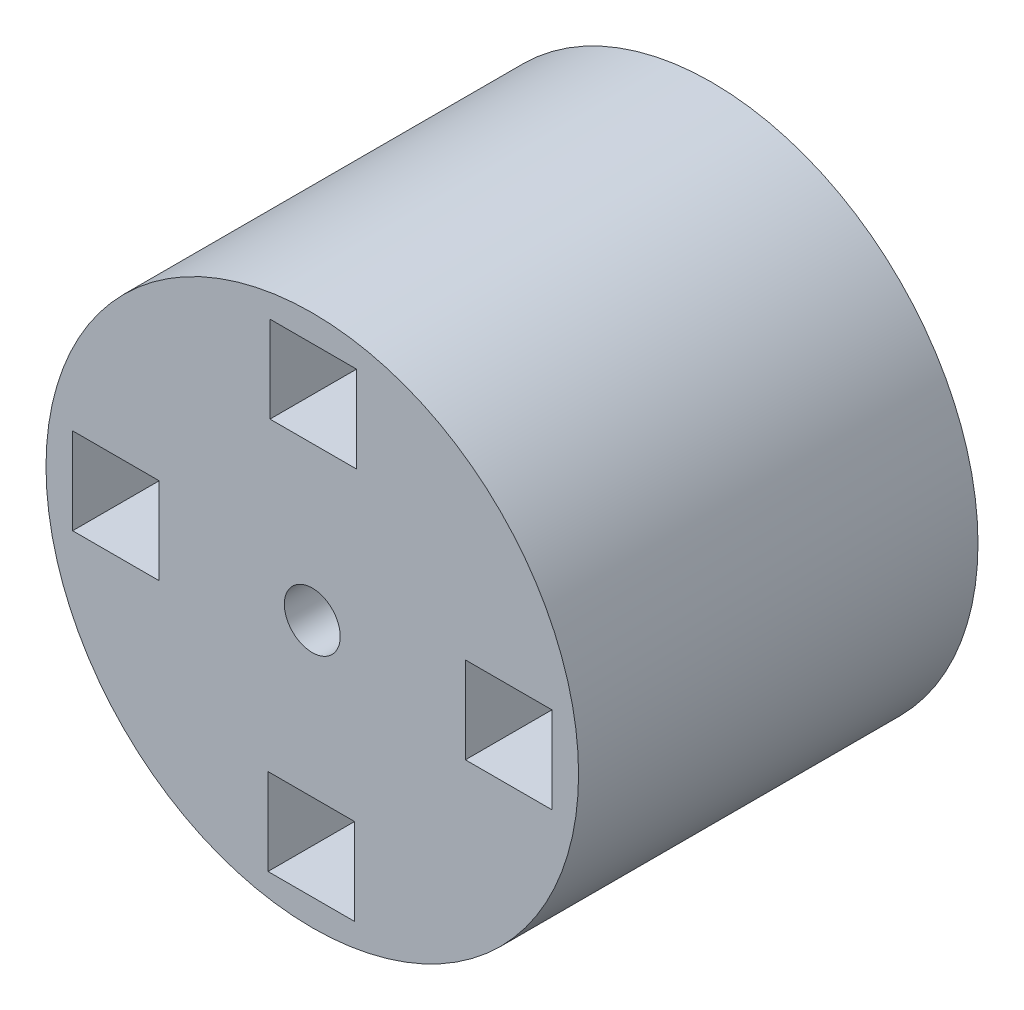
SolidWorks part; units mm, degrees
ref_plane "Front Plane" through (0, 0, 0) normal (0, 0, 1) x (1, 0, 0)
ref_plane "Top Plane" through (0, 0, 0) normal (0, 1, 0) x (1, 0, 0)
ref_plane "Right Plane" through (0, 0, 0) normal (1, 0, 0) x (0, 0, -1)
sketch "Sketch1" plane through (0, 0, 0) normal (0, 0, 1) x (1, 0, 0)
  circle A0 centre (-11.8226, 14.5298) radius 20
  circle A1 centre (-11.8226, 14.5298) radius 1
  dimension "D1" = 40
  dimension "D2" = 2
extrude "Boss-Extrude1" add sketch "Sketch1" along normal blind 30
hole_wizard "Tap Drill for M5x0.8 Tap1" positions "Sketch2" profile "Sketch3" hole size "M5x0.8" standard "ANSI Metric"
sketch "Sketch2" plane through (0, 0, 30) normal (0, 0, 1) x (1, 0, 0)
  point P0 (-11.8226, 14.5298)
sketch "Sketch3" plane through (-11.8226, 14.5298, 30) normal (1, 0, 0) x (0, -1, 0)
  line L0 (0, 0) -> (0, 6.2618)
  line L1 (0, 6.2618) -> (2.1, 5)
  line L2 (2.1, 5) -> (2.1, 0)
  line L5 (2.1, 0) -> (0, 0)
  line L10 (0, 6.2618) -> (-2.1, 5) construction
  line L11 (0, -6.35) -> (0, 107.95) construction
  dimension "Hole Dia." = 4.2
  dimension "Hole Depth" = 5
  dimension "Drill Angle" = 118
sketch "Sketch4" plane through (0, 0, 30) normal (0, 0, 1) x (1, 0, 0)
  line L1 (6.1774, 17.7048) -> (-0.3226, 17.7048)
  line L2 (6.1774, 17.7048) -> (6.1774, 11.2048)
  line L3 (6.1774, 11.2048) -> (-0.3226, 11.2048)
  line L4 (-0.3226, 17.7048) -> (-0.3226, 11.2048)
  circle A0 centre (-11.8226, 14.5298) radius 1 construction
  circle A1 centre (-11.8226, 14.5298) radius 20 construction
  dimension "D1" = 6.5
  dimension "D2" = 6.5
  dimension "D3" = 3.325
  dimension "D4" = 18
extrude "Cut-Extrude1" cut sketch "Sketch4" against normal offset from surface (27.5 mm away) 2.5 up to face at (8.1774, 14.5298, 0)
ref_axis "Axis1" through (-11.8226, 14.5298, 30) along (0, 0, -1)
pattern_circular "CirPattern1" count 4 over 360 about axis through (-11.8226, 14.5298, 30) along (0, 0, -1) of "Cut-Extrude1"
sketch "Sketch5" plane through (0, 0, 0) normal (0, 0, -1) x (-1, 0, 0)
  circle A0 centre (11.8226, 14.5298) radius 5.5
  circle A1 centre (11.8226, 14.5298) radius 6.5
  dimension "D1" = 11
  dimension "D2" = 13
extrude "Cut-Extrude2" cut sketch "Sketch5" against normal blind 1
fillet "Fillet3" radius 0.5 2 edges at (-17.3226, 14.5298, 1) (-18.3226, 14.5298, 1)
equation "\"D2@Sketch4\"=6.5"
equation "\"D3@Sketch4\"=6.65/2"
equation "\"oringdiameter\"= 12"
equation "\"oringthickness\"= 2"
equation "\"D2@Sketch5\"=\"oringdiameter\" + \"oringthickness\"/2"
equation "\"D1@Sketch5\"=\"oringdiameter\" - \"oringthickness\"/2"
equation "\"D1@Cut-Extrude2\"= \"oringthickness\"/2"
equation "\"DC1@Fillet\"=\"oringthickness\" * 0.25"
